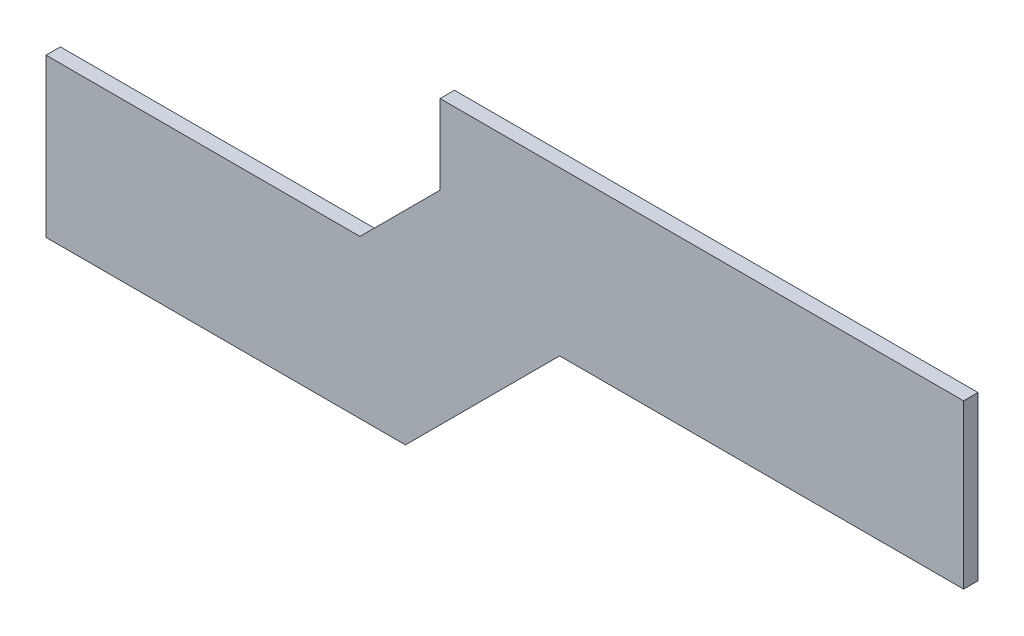
SolidWorks part; units mm, degrees
ref_plane "Спереди" through (0, 0, 0) normal (0, 0, 1) x (1, 0, 0)
ref_plane "Сверху" through (0, 0, 0) normal (0, 1, 0) x (1, 0, 0)
ref_plane "Справа" through (0, 0, 0) normal (1, 0, 0) x (0, 0, -1)
sketch "Эскиз1" plane through (0, 0, 0) normal (0, 0, 1) x (1, 0, 0)
  line L0 (-164.4683, 1.0153) -> (-164.4683, -42.8786)
  line L1 (-54.8861, 45.3538) -> (-54.8861, 23.2989)
  line L2 (-54.8861, 23.2989) -> (-77.1697, 1.0153)
  line L3 (90.7105, 0) -> (-21.6322, 0)
  line L5 (-77.1697, 1.0153) -> (-164.4683, 1.0153)
  line L9 (90.7105, 0) -> (90.7105, 45.3538)
  line L10 (90.7105, 45.3538) -> (-54.8861, 45.3538)
  line L11 (-21.6322, 0) -> (-64.5108, -42.8786)
  line L12 (-64.5108, -42.8786) -> (-164.4683, -42.8786)
extrude "Бобышка-Вытянуть1" add sketch "Эскиз1" along normal blind 4
sketch "Эскиз2"
  dimension "D5" = 3.3
  dimension "D13" = 3.3
  dimension "D15" = 3.3
  dimension "D1" = 10
  dimension "D2" = 10
  dimension "D3" = 10
  dimension "D4" = 10
  dimension "D9" = 5
  dimension "D10" = 5
  dimension "D11" = 5
  dimension "D12" = 5
